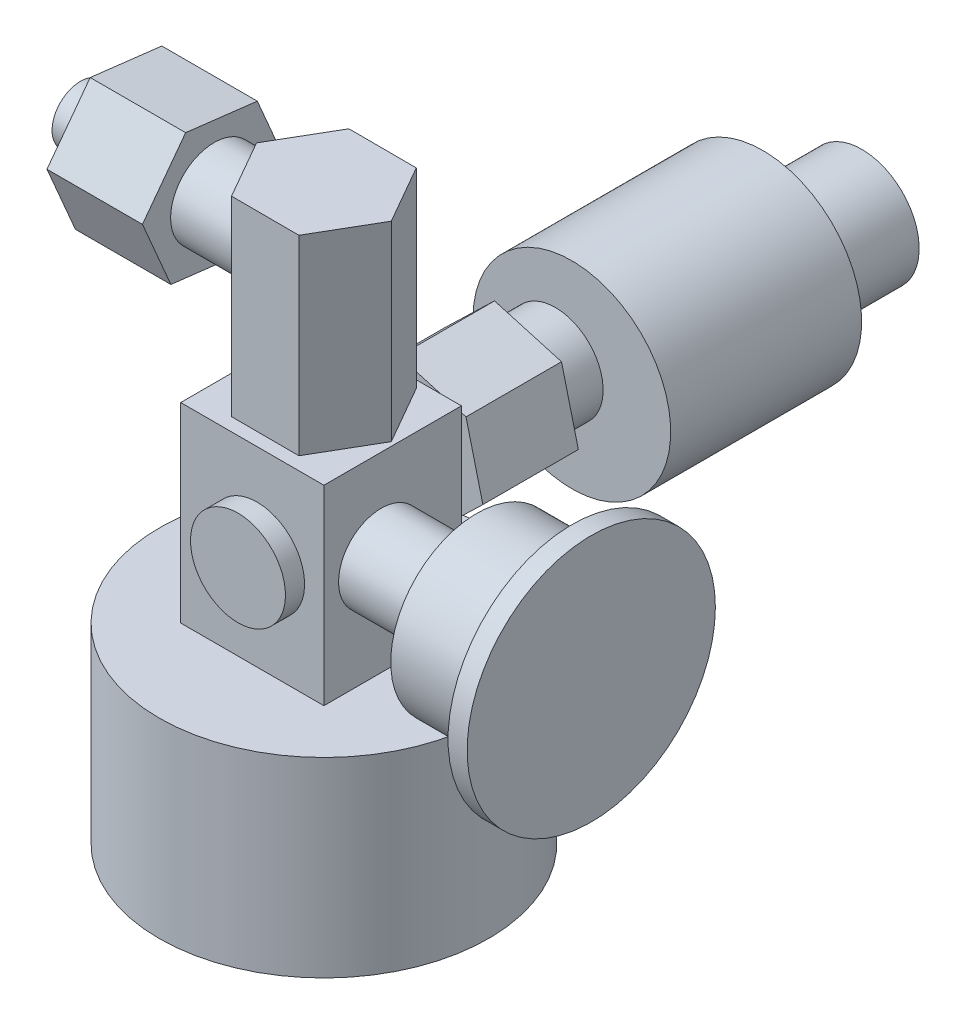
SolidWorks part; units mm, degrees
ref_plane "Front Plane" through (0, 0, 0) normal (0, 0, 1) x (1, 0, 0)
ref_plane "Top Plane" through (0, 0, 0) normal (0, 1, 0) x (1, 0, 0)
ref_plane "Right Plane" through (0, 0, 0) normal (1, 0, 0) x (0, 0, -1)
sketch "Sketch1" plane through (0, 0, 0) normal (0, 1, 0) x (1, 0, 0)
  circle A0 centre (0, 0) radius 21.9075
  point P2 (0, 0)
  dimension "D1" = 43.815
extrude "Boss-Extrude1" add sketch "Sketch1" along normal blind 25.4
sketch "Sketch2" plane through (0, 25.4, 0) normal (0, 1, 0) x (1, 0, 0)
  line L1 (-9.525, 8.763) -> (9.525, 8.763)
  line L2 (-9.525, 8.763) -> (-9.525, -9.525)
  line L3 (-9.525, -9.525) -> (9.525, -9.525)
  line L4 (9.525, 8.763) -> (9.525, -9.525)
  dimension "D1" = 19.05
  dimension "D2" = 18.288
  dimension "D3" = 9.525
  dimension "D4" = 9.525
extrude "Boss-Extrude2" add sketch "Sketch2" along normal blind 25.4
sketch "Sketch3" plane through (0, 0, 9.525) normal (0, 0, 1) x (1, 0, 0)
  line L0 (-9.525, 50.8) -> (-9.525, 25.4) construction
  line L1 (-9.525, 50.8) -> (9.525, 50.8) construction
  circle A0 centre (0.635, 38.1) radius 6.3157
  point P2 (0, 0)
  dimension "D1" = 10.16
  dimension "D2" = 12.7
sketch "Sketch4" plane through (9.525, 0, 0) normal (1, 0, 0) x (0, 0, -1)
  line L0 (-9.525, 50.8) -> (-9.525, 25.4) construction
  circle A0 centre (-1.905, 38.6654) radius 5.6711
  point P2 (0, 0)
  dimension "D1" = 7.62
extrude "Boss-Extrude3" add sketch "Sketch4" along normal blind 12.7
extrude "Boss-Extrude4" add sketch "Sketch3" along normal blind 2.54
sketch "Sketch5" plane through (22.225, 0, 0) normal (1, 0, 0) x (0, 0, -1)
  circle A0 centre (-1.905, 38.6654) radius 11.43
  circle A3 centre (-1.905, 38.6654) radius 5.6711 construction
  dimension "D1" = 22.86
extrude "Boss-Extrude5" add sketch "Sketch5" along normal blind 12.7
sketch "Sketch6" plane through (34.925, 0, 0) normal (1, 0, 0) x (0, 0, -1)
  circle A0 centre (-1.905, 38.6654) radius 16.51
  circle A1 centre (-1.905, 38.6654) radius 11.43 construction
  dimension "D1" = 33.02
extrude "Boss-Extrude6" add sketch "Sketch6" along normal blind 2.54
sketch "Sketch7" plane through (0, 0, -8.763) normal (0, 0, -1) x (-1, 0, 0)
  circle A0 centre (0, 40.8707) radius 6.1008
extrude "Boss-Extrude7" add sketch "Sketch7" along normal blind 2.54
sketch "Sketch8" plane through (0, 0, -11.303) normal (0, 0, -1) x (-1, 0, 0)
  line L7 (7.9728, 43.4181) -> (1.3068, 49.8534)
  line L8 (1.3068, 49.8534) -> (-7.5993, 47.2981)
  line L9 (-7.5993, 47.2981) -> (-9.8393, 38.3076)
  line L10 (-9.8393, 38.3076) -> (-3.1734, 31.8723)
  line L11 (-3.1734, 31.8723) -> (5.7327, 34.4276)
  line L12 (5.7327, 34.4276) -> (7.9728, 43.4181)
  circle A0 centre (-0.9333, 40.8628) radius 8.0241 construction
extrude "Boss-Extrude8" add sketch "Sketch8" along normal blind 12.7
sketch "Sketch9" plane through (0, 0, -24.003) normal (0, 0, -1) x (-1, 0, 0)
  circle A0 centre (-1.7057, 41.7138) radius 6.35
  dimension "D1" = 12.7
extrude "Boss-Extrude9" add sketch "Sketch9" along normal blind 5.08
sketch "Sketch10" plane through (0, 0, -29.083) normal (0, 0, -1) x (-1, 0, 0)
  circle A0 centre (-3.8998, 41.4059) radius 13.1441
extrude "Boss-Extrude10" add sketch "Sketch10" along normal blind 25.4
sketch "Sketch11" plane through (0, 0, -54.483) normal (0, 0, -1) x (-1, 0, 0)
  circle A0 centre (-4.3695, 40.9411) radius 7.62
  dimension "D1" = 15.24
extrude "Boss-Extrude11" add sketch "Sketch11" along normal blind 12.7
sketch "Sketch12" plane through (0, 50.8, 0) normal (0, 1, 0) x (1, 0, 0)
  line L1 (-4.5175, -7.7709) -> (4.471, -7.7977)
  line L2 (4.471, -7.7977) -> (8.9885, -0.0268)
  line L3 (8.9885, -0.0268) -> (4.5175, 7.7709)
  line L4 (4.5175, 7.7709) -> (-4.471, 7.7977)
  line L5 (-4.471, 7.7977) -> (-8.9885, 0.0268)
  line L6 (-8.9885, 0.0268) -> (-4.5175, -7.7709)
  circle A0 centre (0, 0) radius 7.7843 construction
extrude "Boss-Extrude12" add sketch "Sketch12" along normal blind 25.4
sketch "Sketch13" plane through (-9.525, 0, 0) normal (-1, 0, 0) x (0, 0, 1)
  circle A0 centre (0, 67.655) radius 5.7875
extrude "Boss-Extrude13" add sketch "Sketch13" along normal blind 5.08 and the other way blind 5.08
sketch "Sketch14" plane through (-14.605, 0, 0) normal (-1, 0, 0) x (0, 0, 1)
  line L1 (5.747, 59.9668) -> (9.5316, 68.7879)
  line L2 (9.5316, 68.7879) -> (3.7847, 76.4761)
  line L3 (3.7847, 76.4761) -> (-5.747, 75.3432)
  line L4 (-5.747, 75.3432) -> (-9.5316, 66.5221)
  line L5 (-9.5316, 66.5221) -> (-3.7847, 58.8339)
  line L6 (-3.7847, 58.8339) -> (5.747, 59.9668)
  circle A0 centre (0, 67.655) radius 8.3127 construction
extrude "Boss-Extrude14" add sketch "Sketch14" along normal blind 12.7
sketch "Sketch15" plane through (-27.305, 0, 0) normal (-1, 0, 0) x (0, 0, 1)
  circle A0 centre (0, 67.8372) radius 3.7745
extrude "Boss-Extrude15" add sketch "Sketch15" along normal blind 5.08
